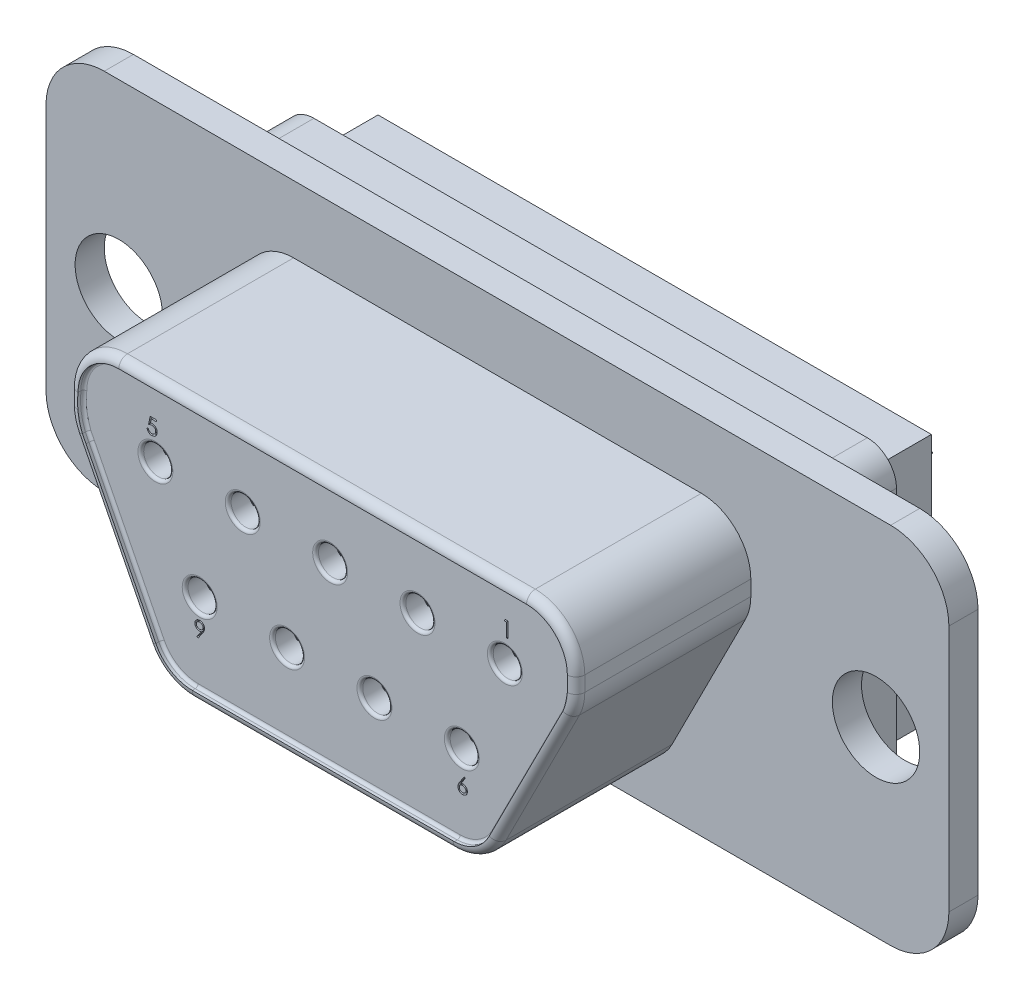
SolidWorks part; units mm, degrees
ref_plane "Front Plane" through (0, 0, 0) normal (0, 0, 1) x (1, 0, 0)
ref_plane "Top Plane" through (0, 0, 0) normal (0, 1, 0) x (1, 0, 0)
ref_plane "Right Plane" through (0, 0, 0) normal (1, 0, 0) x (0, 0, -1)
sketch "Sketch1" plane through (0, 0, 0) normal (0, 0, 1) x (1, 0, 0)
  line L1 (-28.3449, -13.9234) -> (-1.3449, -13.9234)
  line L2 (-30.3449, -15.9234) -> (-30.3449, -24.4234)
  line L3 (-28.3449, -26.4234) -> (-1.3449, -26.4234)
  line L4 (0.6551, -15.9234) -> (0.6551, -24.4234)
  line L6 (-30.3449, -20.1734) -> (0.6551, -20.1734) construction
  line L7 (-14.8449, -13.9234) -> (-14.8449, -26.4234) construction
  arc A0 (-30.3449, -15.9234) -> (-28.3449, -13.9234) centre (-28.3449, -15.9234) cw
  arc A1 (-28.3449, -26.4234) -> (-30.3449, -24.4234) centre (-28.3449, -24.4234) cw
  arc A2 (0.6551, -15.9234) -> (-1.3449, -13.9234) centre (-1.3449, -15.9234) ccw
  arc A3 (-1.3449, -26.4234) -> (0.6551, -24.4234) centre (-1.3449, -24.4234) ccw
  circle A4 centre (-27.8449, -20.1734) radius 1.5
  circle A5 centre (-1.8449, -20.1734) radius 1.5
  dimension "D1" = 2
  dimension "D2" = 26
extrude "Extrude1" add sketch "Sketch1" along normal blind 1
sketch "Sketch2" plane through (0, 0, 1) normal (0, 0, 1) x (1, 0, 0)
  line L0 (-14.8449, -13.9234) -> (-14.8449, -26.4234) construction
  line L5 (-1.3449, -13.9234) -> (-28.3449, -13.9234) construction
  line L6 (-28.3449, -26.4234) -> (-1.3449, -26.4234) construction
  line L9 (-21.8449, -16.2234) -> (-7.8449, -16.2234)
  line L10 (-6.1449, -17.9234) -> (-6.1449, -18.4438)
  line L11 (-6.3282, -19.2116) -> (-8.8492, -24.1913)
  line L12 (-19.324, -25.1234) -> (-10.3659, -25.1234)
  line L13 (-23.3616, -19.2116) -> (-20.8407, -24.1913)
  line L14 (-23.5449, -17.9234) -> (-23.5449, -18.4438)
  arc A6 (-6.1449, -17.9234) -> (-7.8449, -16.2234) centre (-7.8449, -17.9234) ccw
  arc A7 (-6.3282, -19.2116) -> (-6.1449, -18.4438) centre (-7.8449, -18.4438) ccw
  arc A8 (-8.8492, -24.1913) -> (-10.3659, -25.1234) centre (-10.3659, -23.4234) cw
  arc A9 (-20.8407, -24.1913) -> (-19.324, -25.1234) centre (-19.324, -23.4234) ccw
  arc A10 (-23.3616, -19.2116) -> (-23.5449, -18.4438) centre (-21.8449, -18.4438) cw
  arc A11 (-21.8449, -16.2234) -> (-23.5449, -17.9234) centre (-21.8449, -17.9234) ccw
  point P14 (-20.5531, -25.4234)
  point P17 (-9.1367, -25.4234)
  point P20 (-5.8449, -15.9234)
  point P26 (-23.8449, -15.9234)
  point P29 (-23.8449, -18.9212)
  dimension "D1" = 18
extrude "Extrude2" add sketch "Sketch2" along normal blind 6
sketch "Sketch3" plane through (0, 0, 0) normal (0, 0, -1) x (-1, 0, 0)
  line L0 (14.8449, -13.9234) -> (14.8449, -26.4234) construction
  line L1 (1.3449, -13.9234) -> (28.3449, -13.9234) construction
  line L2 (28.3449, -26.4234) -> (1.3449, -26.4234) construction
  line L4 (30.3449, -15.9234) -> (30.3449, -24.4234) construction
  line L5 (30.3449, -20.1734) -> (-0.6551, -20.1734) construction
  line L6 (-0.6551, -24.4234) -> (-0.6551, -15.9234) construction
  line L9 (25.3449, -15.9234) -> (25.3449, -24.4234)
  line L10 (5.3449, -14.9234) -> (24.3449, -14.9234)
  line L11 (4.3449, -15.9234) -> (4.3449, -24.4234)
  line L12 (5.3449, -25.4234) -> (24.3449, -25.4234)
  arc A0 (5.3449, -14.9234) -> (4.3449, -15.9234) centre (5.3449, -15.9234) ccw
  arc A1 (25.3449, -15.9234) -> (24.3449, -14.9234) centre (24.3449, -15.9234) ccw
  arc A2 (24.3449, -25.4234) -> (25.3449, -24.4234) centre (24.3449, -24.4234) ccw
  arc A3 (4.3449, -24.4234) -> (5.3449, -25.4234) centre (5.3449, -24.4234) ccw
  point P18 (4.3449, -14.9234)
  point P21 (25.3449, -14.9234)
  point P24 (25.3449, -25.4234)
  point P27 (4.3449, -25.4234)
  dimension "D3" = 1
  dimension "D1" = 1
  dimension "D2" = 1
extrude "Extrude3" add sketch "Sketch3" along normal blind 2.2
sketch "Sketch4" plane through (0, 0, -2.2) normal (0, 0, -1) x (-1, 0, 0)
  line L0 (14.8449, -14.9234) -> (14.8449, -25.4234) construction
  line L1 (24.3449, -14.9234) -> (5.3449, -14.9234) construction
  line L2 (5.3449, -25.4234) -> (24.3449, -25.4234) construction
  line L3 (4.3449, -15.9234) -> (4.3449, -24.4234) construction
  line L4 (5.3449, -15.9234) -> (24.3449, -15.9234)
  line L5 (5.3449, -15.9234) -> (5.3449, -24.4234)
  line L6 (5.3449, -24.4234) -> (24.3449, -24.4234)
  line L7 (24.3449, -15.9234) -> (24.3449, -24.4234)
  point P13 (14.8449, -24.4234)
  point P14 (14.8449, -15.9234)
  dimension "D1" = 1
  dimension "D2" = 1
  dimension "D3" = 1
extrude "Extrude4" add sketch "Sketch4" along normal blind 2.2
sketch "Sketch9" plane through (0, 0, -4.4) normal (0, 0, -1) x (-1, 0, 0)
  circle A0 centre (8.7702, -19.0817) radius 0.5
  circle A1 centre (11.7702, -19.0817) radius 0.5
  circle A2 centre (17.7702, -19.0817) radius 0.5
  circle A3 centre (14.7702, -19.0817) radius 0.5
  circle A4 centre (16.2629, -21.8211) radius 0.5
  circle A5 centre (13.2629, -21.8211) radius 0.5
  circle A6 centre (19.2629, -21.8211) radius 0.5
  circle A7 centre (10.2629, -21.8211) radius 0.5
  circle A8 centre (20.7702, -19.0817) radius 0.5
extrude "Extrude-Thin1" add sketch "Sketch9" along normal blind 3 thin thin type one direction wall 0.1
sketch "Sketch10" plane through (-5.3449, 0, 0) normal (1, 0, 0) x (0, 0, -1)
  line L0 (6.1125, -17.939) -> (7.9954, -20.1483)
  line L1 (7.9954, -20.1483) -> (7.9954, -17.939)
  line L2 (7.9954, -17.939) -> (6.1125, -17.939)
  line L3 (7.9954, -20.6784) -> (6.1125, -20.6784)
  line L4 (6.1125, -20.6784) -> (7.9954, -22.8877)
  line L5 (7.9954, -22.8877) -> (7.9954, -20.6784)
extrude "Cut-Extrude2" cut sketch "Sketch10" against normal up to vertex (19 mm away) up to point (-24.3449, -24.4234, -4.4)
fillet "Fillet1" radius 0.3 12 edges at (-14.8449, -16.2234, 7) (-6.6428, -16.7213, 7) (-6.1449, -18.1836, 7) (-6.1914, -18.8385, 7) (-7.5887, -21.7015, 7) (-9.4758, -24.8718, 7) (-14.8449, -25.1234, 7) (-20.2141, -24.8718, 7) (-22.1012, -21.7015, 7) (-23.4985, -18.8385, 7) (-23.5449, -18.1836, 7) (-23.047, -16.7213, 7)
sketch "Sketch12" plane through (0, 0, 7) normal (0, 0, 1) x (1, 0, 0)
  line L0 (-21.8449, -16.5234) -> (-7.8449, -16.5234)
  line L1 (-6.5838, -19.0517) -> (-9.1437, -24.0904)
  line L2 (-19.324, -24.8234) -> (-10.3241, -24.8221)
  line L3 (-22.9707, -19.3179) -> (-20.573, -24.0558)
  line L4 (-21.8342, -16.0234) -> (-7.8038, -16.0234) construction
  line L5 (-6.138, -19.2781) -> (-8.699, -24.3188) construction
  line L6 (-19.208, -25.3234) -> (-10.3198, -25.3221) construction
  line L7 (-23.3762, -19.624) -> (-21.0715, -24.1782) construction
  line L8 (-7.8449, -16.5234) -> (-21.8449, -16.5234) construction
  line L9 (-22.9707, -19.3179) -> (-23.094, -19.0761)
  arc A0 (-6.4449, -17.9234) -> (-7.8449, -16.5234) centre (-7.8449, -17.9234) ccw
  arc A1 (-9.1437, -24.0904) -> (-10.3241, -24.8221) centre (-10.3492, -23.4637) cw
  arc A2 (-20.573, -24.0558) -> (-19.324, -24.8234) centre (-19.3242, -23.4238) ccw
  arc A4 (-7.8038, -16.0234) -> (-6.138, -19.2781) centre (-8.1517, -18.2551) cw construction
  arc A5 (-8.699, -24.3188) -> (-10.3198, -25.3221) centre (-10.3492, -23.4637) cw construction
  arc A6 (-23.2449, -17.9234) -> (-21.8449, -16.5234) centre (-21.8449, -17.9234) cw
  arc A7 (-21.8342, -16.0234) -> (-23.3762, -19.624) centre (-21.9187, -18.1177) ccw construction
  arc A8 (-6.4449, -17.9234) -> (-7.8449, -16.5234) centre (-7.8449, -17.9234) ccw construction
  arc A9 (-6.5959, -19.0761) -> (-6.4449, -18.4438) centre (-7.8449, -18.4438) ccw construction
  arc A10 (-21.0715, -24.1782) -> (-19.208, -25.3234) centre (-19.7373, -24.096) ccw construction
  arc A11 (-20.573, -24.0558) -> (-19.324, -24.8234) centre (-19.7373, -24.096) ccw construction
  arc A12 (-21.8449, -16.5234) -> (-22.9707, -19.3179) centre (-21.9187, -18.1177) ccw construction
  arc A13 (-23.2449, -17.9234) -> (-23.094, -19.0761) centre (-20.9082, -18.2037) ccw
  arc A14 (-7.8449, -16.5234) -> (-6.5838, -19.0517) centre (-8.1517, -18.2551) cw construction
  arc A15 (-6.4449, -17.9234) -> (-6.5838, -19.0517) centre (-9.0139, -18.1799) cw
  dimension "D1" = 0.5
extrude "Cut-Extrude4" cut sketch "Sketch12" against normal blind 0.2
sketch "Sketch13" plane through (0, 0, 6.8) normal (0, 0, 1) x (1, 0, 0)
  circle A0 centre (-20.7893, -18.8539) radius 0.5
  circle A1 centre (-17.7893, -18.8539) radius 0.5
  circle A2 centre (-14.7893, -18.8539) radius 0.5
  circle A3 centre (-11.7893, -18.8539) radius 0.5
  circle A4 centre (-8.7893, -18.8539) radius 0.5
  circle A5 centre (-10.2681, -22.1216) radius 0.5
  circle A6 centre (-13.2681, -22.1216) radius 0.5
  circle A7 centre (-16.2681, -22.1216) radius 0.5
  circle A8 centre (-19.2681, -22.1216) radius 0.5
extrude "Cut-Extrude5" cut sketch "Sketch13" against normal blind 5.2
fillet "Fillet2" radius 0.1 20 edges at (-14.8449, -16.5234, 6.8) (-7.8638, -21.571, 6.8) (-9.6334, -24.6185, 6.8) (-14.824, -24.8228, 6.8) (-21.7719, -21.6868, 6.8) (-20.2893, -18.8539, 6.8) (-17.2893, -18.8539, 6.8) (-14.2893, -18.8539, 6.8) (-11.2893, -18.8539, 6.8) (-8.2893, -18.8539, 6.8) (-9.7681, -22.1216, 6.8) (-12.7681, -22.1216, 6.8) (-15.7681, -22.1216, 6.8) (-18.7681, -22.1216, 6.8) (-6.855, -16.9335, 6.8) (-6.4515, -18.4953, 6.8) (-20.057, -24.6162, 6.8) (-23.0324, -19.197, 6.8) (-23.2418, -18.5092, 6.8) (-22.8349, -16.9335, 6.8)
sketch "Sketch16" plane through (0, 0, 1.6) normal (0, 0, 1) x (1, 0, 0)
  line L0 (-20.7893, -18.3539) -> (-20.7893, -18.5598) construction
  line L1 (-17.7857, -18.3534) -> (-17.7857, -18.5598) construction
  line L2 (-14.7857, -18.3534) -> (-14.7857, -18.5598) construction
  line L3 (-11.7857, -18.3534) -> (-11.7857, -18.5598) construction
  line L4 (-8.7857, -18.3534) -> (-8.7857, -18.5598) construction
  line L5 (-10.2664, -21.6092) -> (-10.2664, -21.8156) construction
  line L6 (-13.2664, -21.6092) -> (-13.2664, -21.8156) construction
  line L7 (-16.2664, -21.6092) -> (-16.2664, -21.8156) construction
  line L8 (-19.2664, -21.6092) -> (-19.2664, -21.8156) construction
  arc A0 (-21.1594, -18.5808) -> (-21.1226, -19.1732) centre (-20.6864, -18.8488) ccw
  arc A1 (-21.1594, -18.5808) -> (-21.1226, -19.1732) centre (-20.8794, -18.8607) ccw
  circle A2 centre (-20.7893, -18.8539) radius 0.5 construction
  arc A3 (-20.4192, -18.5808) -> (-20.456, -19.1732) centre (-20.6992, -18.8607) cw
  arc A4 (-20.4192, -18.5808) -> (-20.456, -19.1732) centre (-20.8921, -18.8488) cw
  arc A5 (-17.4121, -18.5808) -> (-17.4567, -19.1834) centre (-17.6552, -18.8658) cw
  arc A6 (-17.4121, -18.5808) -> (-17.4567, -19.1834) centre (-17.885, -18.8488) cw
  arc A7 (-18.1594, -18.5808) -> (-18.1147, -19.1834) centre (-17.6864, -18.8488) ccw
  arc A8 (-18.1594, -18.5808) -> (-18.1147, -19.1834) centre (-17.9163, -18.8658) ccw
  arc A9 (-14.4121, -18.5808) -> (-14.4567, -19.1834) centre (-14.6552, -18.8658) cw
  arc A10 (-14.4121, -18.5808) -> (-14.4567, -19.1834) centre (-14.885, -18.8488) cw
  arc A11 (-15.1594, -18.5808) -> (-15.1147, -19.1834) centre (-14.6864, -18.8488) ccw
  arc A12 (-15.1594, -18.5808) -> (-15.1147, -19.1834) centre (-14.9163, -18.8658) ccw
  arc A13 (-11.4121, -18.5808) -> (-11.4567, -19.1834) centre (-11.6552, -18.8658) cw
  arc A14 (-11.4121, -18.5808) -> (-11.4567, -19.1834) centre (-11.885, -18.8488) cw
  arc A15 (-12.1594, -18.5808) -> (-12.1147, -19.1834) centre (-11.6864, -18.8488) ccw
  arc A16 (-12.1594, -18.5808) -> (-12.1147, -19.1834) centre (-11.9163, -18.8658) ccw
  arc A17 (-8.4121, -18.5808) -> (-8.4567, -19.1834) centre (-8.6552, -18.8658) cw
  arc A18 (-8.4121, -18.5808) -> (-8.4567, -19.1834) centre (-8.885, -18.8488) cw
  arc A19 (-9.1594, -18.5808) -> (-9.1147, -19.1834) centre (-8.6864, -18.8488) ccw
  arc A20 (-9.1594, -18.5808) -> (-9.1147, -19.1834) centre (-8.9163, -18.8658) ccw
  arc A21 (-9.8927, -21.8366) -> (-9.9374, -22.4392) centre (-10.1358, -22.1216) cw
  arc A22 (-9.8927, -21.8366) -> (-9.9374, -22.4392) centre (-10.3657, -22.1045) cw
  arc A23 (-10.64, -21.8366) -> (-10.5954, -22.4392) centre (-10.167, -22.1045) ccw
  arc A24 (-10.64, -21.8366) -> (-10.5954, -22.4392) centre (-10.3969, -22.1216) ccw
  arc A25 (-12.8927, -21.8366) -> (-12.9374, -22.4392) centre (-13.1358, -22.1216) cw
  arc A26 (-12.8927, -21.8366) -> (-12.9374, -22.4392) centre (-13.3657, -22.1045) cw
  arc A27 (-13.64, -21.8366) -> (-13.5954, -22.4392) centre (-13.167, -22.1045) ccw
  arc A28 (-13.64, -21.8366) -> (-13.5954, -22.4392) centre (-13.3969, -22.1216) ccw
  arc A29 (-15.8927, -21.8366) -> (-15.9374, -22.4392) centre (-16.1358, -22.1216) cw
  arc A30 (-15.8927, -21.8366) -> (-15.9374, -22.4392) centre (-16.3657, -22.1045) cw
  arc A31 (-16.64, -21.8366) -> (-16.5954, -22.4392) centre (-16.167, -22.1045) ccw
  arc A32 (-16.64, -21.8366) -> (-16.5954, -22.4392) centre (-16.3969, -22.1216) ccw
  arc A33 (-18.8927, -21.8366) -> (-18.9374, -22.4392) centre (-19.1358, -22.1216) cw
  arc A34 (-18.8927, -21.8366) -> (-18.9374, -22.4392) centre (-19.3657, -22.1045) cw
  arc A35 (-19.64, -21.8366) -> (-19.5954, -22.4392) centre (-19.167, -22.1045) ccw
  arc A36 (-19.64, -21.8366) -> (-19.5954, -22.4392) centre (-19.3969, -22.1216) ccw
extrude "Boss-Extrude1" add sketch "Sketch16" along normal blind 4.5
sketch "Sketch17" plane through (0, 0, 6.8) normal (0, 0, 1) x (1, 0, 0)
  text T0 "1" font "Century Gothic" height in points 2
sketch "Sketch18" plane through (0, 0, 6.8) normal (0, 0, 1) x (1, 0, 0)
  text T0 "5" font "Century Gothic" height in points 2
sketch "Sketch19" plane through (0, 0, 6.8) normal (0, 0, 1) x (1, 0, 0)
  text T0 "6" font "Century Gothic" height in points 2
sketch "Sketch20" plane through (0, 0, 6.8) normal (0, 0, 1) x (1, 0, 0)
  text T0 "9" font "Century Gothic" height in points 2
extrude "Cut-Extrude6" cut sketch "Sketch17" against normal blind 0.1
extrude "Cut-Extrude7" cut sketch "Sketch18" against normal blind 0.1
extrude "Cut-Extrude8" cut sketch "Sketch20" against normal blind 0.1
extrude "Cut-Extrude9" cut sketch "Sketch19" against normal blind 0.1
